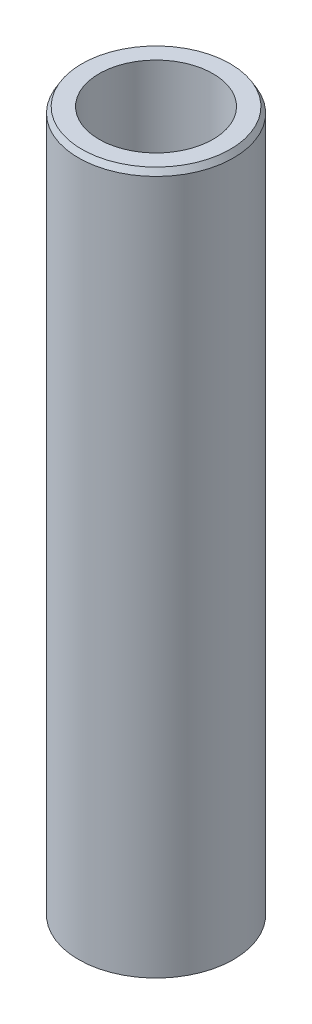
SolidWorks part; units mm, degrees
ref_plane "Front Plane" through (0, 0, 0) normal (0, 0, 1) x (1, 0, 0)
ref_plane "Top Plane" through (0, 0, 0) normal (0, 1, 0) x (1, 0, 0)
ref_plane "Right Plane" through (0, 0, 0) normal (1, 0, 0) x (0, 0, -1)
sketch "Sketch1" plane through (0, 0, 0) normal (0, 1, 0) x (1, 0, 0)
  circle A0 centre (0, 0) radius 32.5
  dimension "SHAFT_OD" = 65
extrude "Boss-Extrude1" add sketch "Sketch1" along normal blind 294.8506
sketch "Sketch2" plane through (0, 0, 0) normal (0, 1, 0) x (1, 0, 0)
  circle A0 centre (0, 0) radius 23.8724
  dimension "BORE_D" = 47.7449
extrude "Cut-Extrude1" cut sketch "Sketch2" along normal through all
chamfer "Chamfer1" distance 2.4178 angle 30 2 edges at (0, 294.8506, 32.5) (0, 0, 32.5) first distance on face at (0, 294.8506, 32.5) first distance on face at (0, 0, 23.8724)
